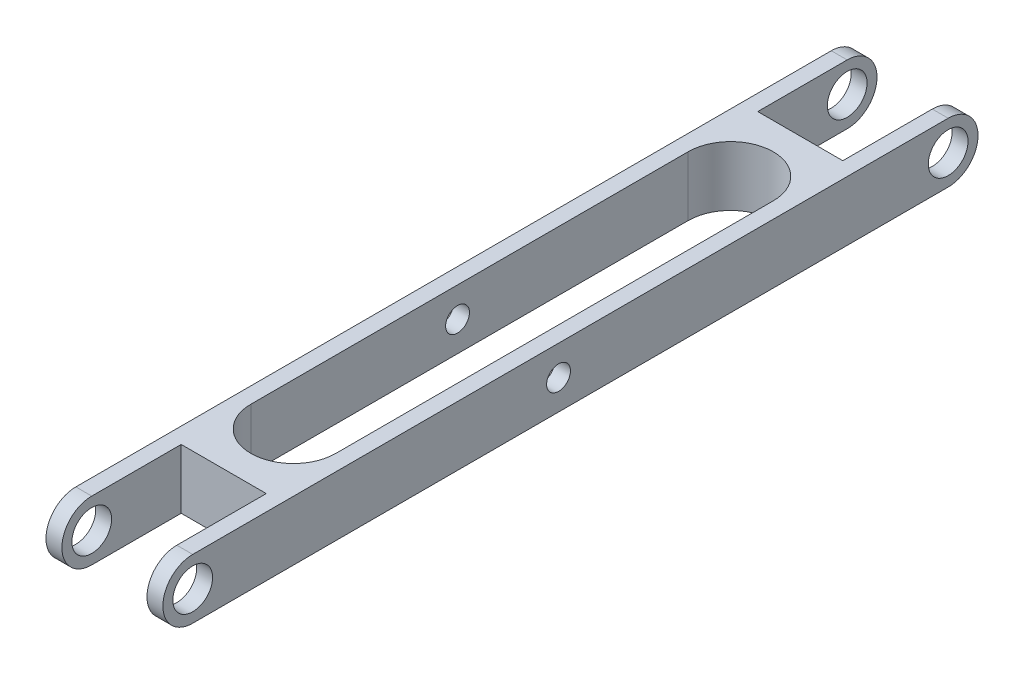
SolidWorks part; units mm, degrees
material "ABS"
ref_plane "前视基准面" through (0, 0, 0) normal (0, 0, 1) x (1, 0, 0)
ref_plane "上视基准面" through (0, 0, 0) normal (0, 1, 0) x (1, 0, 0)
ref_plane "右视基准面" through (0, 0, 0) normal (1, 0, 0) x (0, 0, -1)
sketch "草图2" plane through (0, 0, 0) normal (1, 0, 0) x (0, 0, -1)
  line L0 (-95, 7.5) -> (-95, -7.5) construction
  line L1 (-95, -7.5) -> (95, -7.5)
  line L3 (-95, 7.5) -> (95, 7.5)
  line L5 (-95, -7.5) -> (95, 7.5) construction
  line L6 (-95, 7.5) -> (95, -7.5) construction
  line L7 (95, 7.5) -> (95, -7.5) construction
  arc A0 (-95, 7.5) -> (-95, -7.5) centre (-95, 0) ccw
  arc A1 (95, 7.5) -> (95, -7.5) centre (95, 0) cw
  point P0 (0, 0)
  dimension "D1" = 15
  dimension "D2" = 190
extrude "凸台-拉伸1" add sketch "草图2" along normal blind 29.4
sketch "草图3" plane through (0, 7.5, 0) normal (0, 1, 0) x (1, 0, 0)
  line L1 (4, -102.5) -> (4, -72.5)
  line L2 (0, -102.5) -> (29.4, -102.5) construction
  line L3 (4, -72.5) -> (25.4, -72.5)
  line L4 (25.4, -72.5) -> (25.4, -102.5)
  line L5 (25.4, -102.5) -> (4, -102.5)
  line L6 (0, 95) -> (0, -95) construction
  line L7 (29.4, 95) -> (29.4, -95) construction
  line L10 (4, 102.5) -> (25.4, 102.5)
  line L14 (4, 102.5) -> (4, 72.5)
  line L15 (4, 72.5) -> (25.4, 72.5)
  line L16 (25.4, 72.5) -> (25.4, 102.5)
  line L17 (29.4, 95) -> (0, 95) construction
  dimension "D1" = 4
  dimension "D2" = 4
  dimension "D3" = 30
  dimension "D4" = 21.4
  dimension "D5" = 30
  dimension "D6" = 7.5
  dimension "D7" = 4
extrude "切除-拉伸1" cut sketch "草图3" against normal through all
sketch "草图4" plane through (29.4, 0, 0) normal (1, 0, 0) x (0, 0, -1)
  circle A0 centre (-95, 0) radius 5
  circle A1 centre (95, 0) radius 5
  dimension "D1" = 10
  dimension "D2" = 10
extrude "切除-拉伸2" cut sketch "草图4" against normal through all
sketch "草图5" plane through (0, -7.5, 0) normal (0, -1, 0) x (1, 0, 0)
  line L0 (14.7, 55) -> (14.7, -55) construction
  line L1 (25.4, 55) -> (25.4, -55)
  line L2 (4, 55) -> (4, -55)
  line L3 (0, 0) -> (14.7, 0) construction
  line L4 (0, 95) -> (0, -95) construction
  arc A0 (25.4, 55) -> (4, 55) centre (14.7, 55) ccw
  arc A1 (4, -55) -> (25.4, -55) centre (14.7, -55) ccw
  point P2 (14.7, 0)
  dimension "D1" = 21.4
  dimension "D2" = 14.7
  dimension "D3" = 110
extrude "切除-拉伸3" cut sketch "草图5" against normal through all
sketch "草图6" plane through (0, 0, 0) normal (-1, 0, 0) x (0, 0, 1)
  line L0 (3, 0) -> (0, 0) construction
  circle A1 centre (3, 0) radius 3
  circle A3 centre (95, 0) radius 5 construction
  dimension "D1" = 92
  dimension "D2" = 6
extrude "切除-拉伸4" cut sketch "草图6" against normal through all
